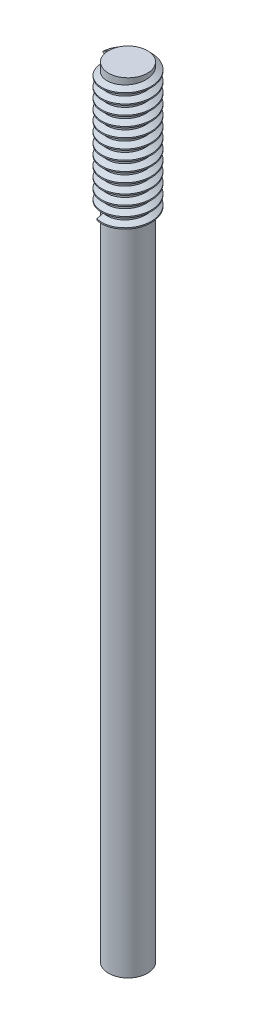
SolidWorks part; units mm, degrees
material "1060 合金"
ref_plane "前视基准面" through (0, 0, 0) normal (0, 0, 1) x (1, 0, 0)
ref_plane "上视基准面" through (0, 0, 0) normal (0, 1, 0) x (1, 0, 0)
ref_plane "右视基准面" through (0, 0, 0) normal (1, 0, 0) x (0, 0, -1)
sketch "草图1" plane through (0, 0, 0) normal (0, 1, 0) x (1, 0, 0)
  circle A0 centre (0, 0) radius 2.5
  dimension "D1" = 5
extrude "凸台-拉伸1" add sketch "草图1" along normal blind 100
thread "螺纹线1" pitch 1.25 method extrude profile "螺纹线轮廓1" start angle 0, offset 0, length 16, pitch 1.25, diameter 5
ref_plane "基准面1" through (-2.5, 100, 0) normal (0, 0, 1) x (-1, 0, 0)
sketch "螺纹线轮廓1" plane through (-2.5, 100, 0) normal (0, 0, 1) x (-1, 0, 0)
  line L0 (0, 0) -> (0, 1.25) construction
  line L1 (0, 0) -> (0.6766, 0.3906)
  line L2 (0.6766, 0.3906) -> (0.6766, 0.5469)
  line L3 (0.6766, 0.5469) -> (0, 0.9375)
  line L4 (0.6766, 0.4687) -> (0, 0.4687) construction
  line L11 (0, 0) -> (0, 0.9375)
  point P2 (0, 0)
  dimension "Pitch" = 1.25
  dimension "Profile_Angle" = 60
  dimension "Profile_Land" = 0.1562
  dimension "Profile_Height" = 0.6766
